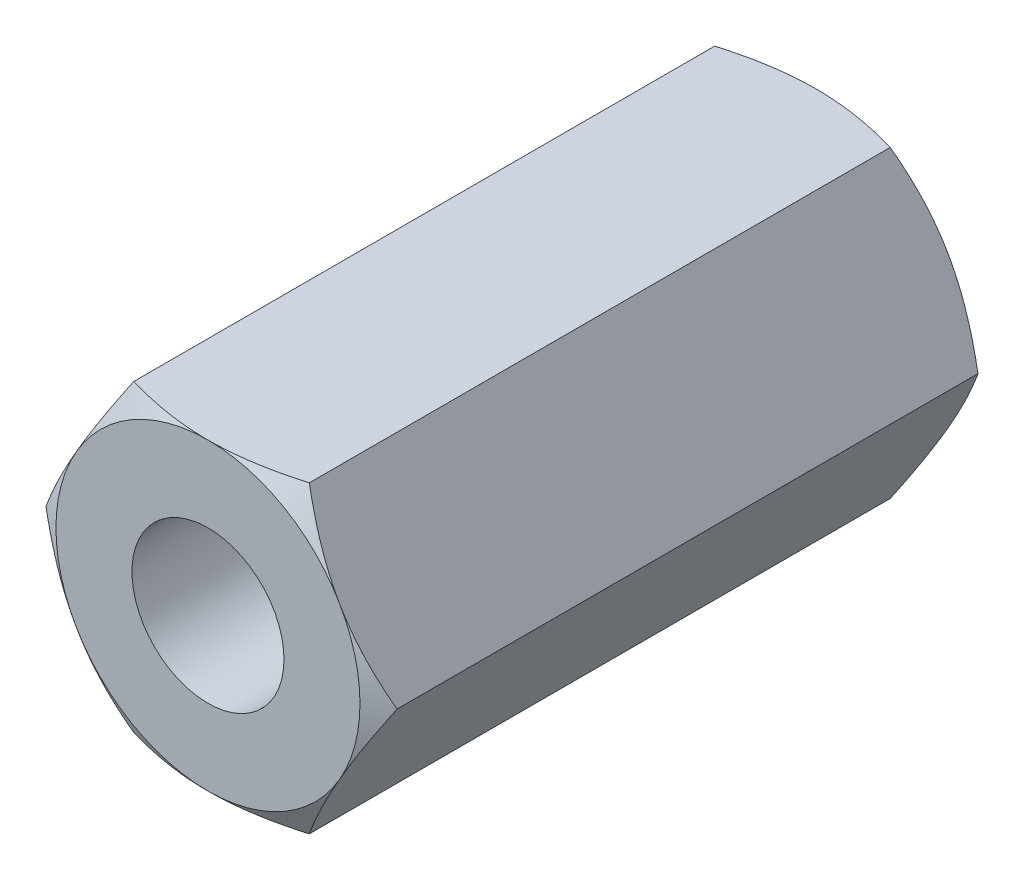
SolidWorks part; units mm, degrees
material "AISI 304"
ref_plane "Front Plane" through (0, 0, 0) normal (0, 0, 1) x (1, 0, 0)
ref_plane "Top Plane" through (0, 0, 0) normal (0, 1, 0) x (1, 0, 0)
ref_plane "Right Plane" through (0, 0, 0) normal (1, 0, 0) x (0, 0, -1)
ref_axis "Axis1" through (0, 0, -52.8182) along (0, 0, 1)
ref_axis "Axis2" through (0, -15.5981, 0) along (0, 1, 0)
ref_axis "Axis3" through (-12.2581, 0, 0) along (1, 0, 0)
sketch "Sketch1" plane through (0, 0, 0) normal (1, 0, 0) x (0, 0, -1)
  line L0 (-6, 0) -> (-6, 3)
  line L1 (-5.567, 3.75) -> (5.567, 3.75)
  line L2 (6, 3) -> (6, 0)
  line L3 (-6, 3) -> (-5.567, 3.75)
  line L4 (0, 0) -> (0, 3.75) construction
  line L5 (6, 0) -> (-6, 0)
  line L6 (-5.5849, 0) -> (13.8966, 0) construction
  line L7 (6, 3) -> (5.567, 3.75)
  dimension "D1" = 30
  dimension "D2" = 7.5
  dimension "D3" = 6
  dimension "LENGTH" = 12
revolve "Revolve1" add sketch "Sketch1" angle 360 about L6
sketch "Sketch2" plane through (0, 0, 6) normal (0, 0, 1) x (1, 0, 0)
  line L1 (1.7321, -3) -> (3.4641, 0)
  line L2 (3.4641, 0) -> (1.7321, 3)
  line L3 (1.7321, 3) -> (-1.7321, 3)
  line L4 (-1.7321, 3) -> (-3.4641, 0)
  line L5 (-3.4641, 0) -> (-1.7321, -3)
  line L6 (-1.7321, -3) -> (1.7321, -3)
  circle A0 centre (0, 0) radius 3 construction
  dimension "D1" = 6
extrude "Cut-Extrude1" cut sketch "Sketch2" against normal through all flip side to cut
hole_wizard "M3x0.5 Tapped Hole1" positions "Sketch4" profile "Sketch3" tap size "M3x0.5" standard "ANSI Metric"
sketch "Sketch4" plane through (0, 0, 6) normal (0, 0, 1) x (1, 0, 0)
  point P0 (0, 0)
sketch "Sketch3" plane through (0, 0, 6) normal (1, 0, 0) x (0, -1, 0)
  line L0 (0, 0) -> (0, 11.7511)
  line L1 (0, 11.7511) -> (1.25, 11)
  line L2 (1.25, 11) -> (1.25, 10)
  line L3 (1.25, 10) -> (1.5, 10)
  line L4 (1.5, 10) -> (1.5, 0)
  line L5 (1.5, 0) -> (0, 0)
  line L10 (0, 11.7511) -> (-1.25, 11) construction
  line L11 (0, -6.35) -> (0, 107.95) construction
  dimension "Tap Drill Dia." = 2.5
  dimension "Tap Drill Depth" = 11
  dimension "Thread Major Dia." = 3
  dimension "Thread Depth" = 10
  dimension "Drill Angle" = 118
hole_wizard "M3x0.5 Tapped Hole2" positions "Sketch6" profile "Sketch5" tap size "M3x0.5" standard "ANSI Metric"
sketch "Sketch6" plane through (0, 0, -6) normal (0, 0, -1) x (-1, 0, 0)
  point P0 (0, 0)
sketch "Sketch5" plane through (0, 0, -6) normal (1, 0, 0) x (0, 1, 0)
  line L0 (0, 0) -> (0, 8.0511)
  line L1 (0, 8.0511) -> (1.25, 7.3)
  line L2 (1.25, 7.3) -> (1.25, 6.3)
  line L3 (1.25, 6.3) -> (1.5, 6.3)
  line L4 (1.5, 6.3) -> (1.5, 0)
  line L5 (1.5, 0) -> (0, 0)
  line L10 (0, 8.0511) -> (-1.25, 7.3) construction
  line L11 (0, -6.35) -> (0, 107.95) construction
  dimension "Tap Drill Dia." = 2.5
  dimension "Tap Drill Depth" = 7.3
  dimension "Thread Major Dia." = 3
  dimension "Thread Depth" = 6.3
  dimension "Drill Angle" = 118
